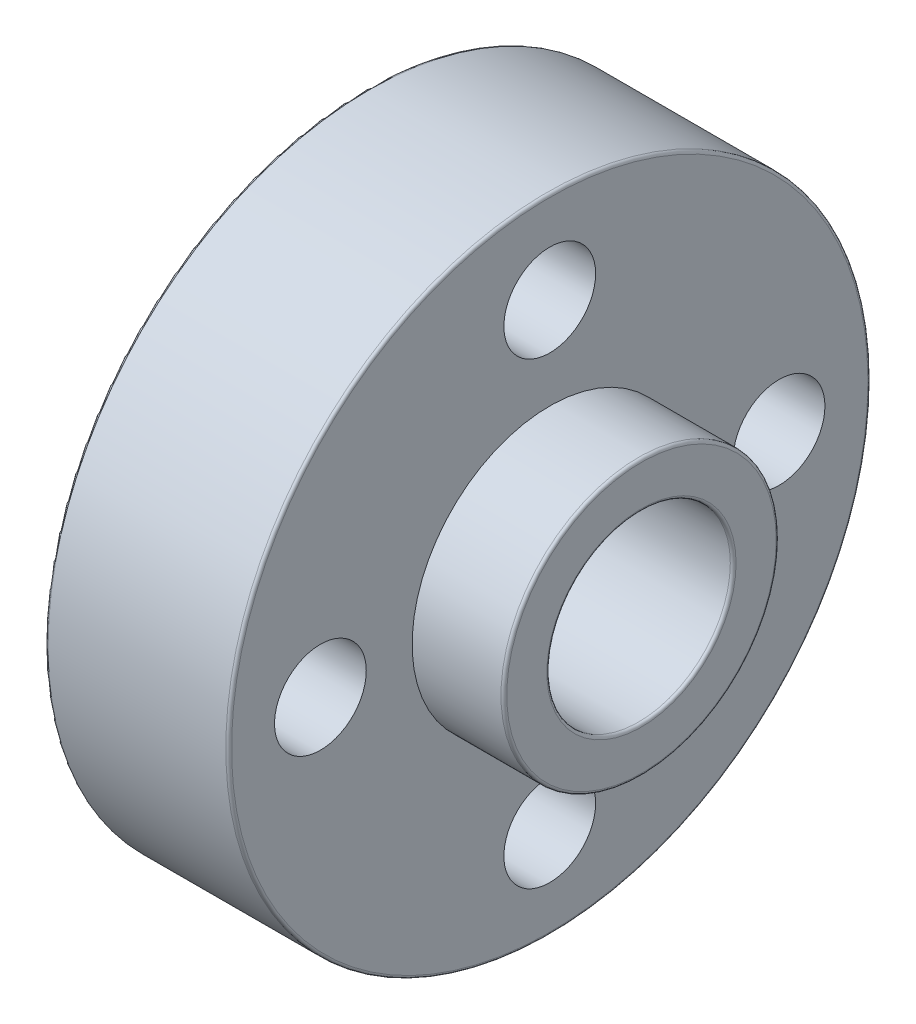
SolidWorks part; units mm, degrees
ref_plane "Front" through (0, 0, 0) normal (0, 0, 1) x (1, 0, 0)
ref_plane "Top" through (0, 0, 0) normal (0, 1, 0) x (1, 0, 0)
ref_plane "Right" through (0, 0, 0) normal (1, 0, 0) x (0, 0, -1)
sketch "Sketch1" plane through (0, 0, 0) normal (1, 0, 0) x (0, 0, -1)
  circle A0 centre (0, 0) radius 11.1125
  dimension "D1" = 22.225
extrude "Boss-Extrude1" add sketch "Sketch1" against normal blind 3.175
sketch "Sketch2" plane through (0, 0, 0) normal (1, 0, 0) x (0, 0, -1)
  circle A0 centre (0, 0) radius 4.7625
  dimension "D1" = 9.525
extrude "Boss-Extrude2" add sketch "Sketch2" along normal blind 3.175
sketch "Sketch4" plane through (3.175, 0, 0) normal (1, 0, 0) x (0, 0, -1)
  circle A0 centre (0, 0) radius 3.175
  dimension "D1" = 6.35
extrude "Cut-Extrude2" cut sketch "Sketch4" against normal through all
mirror "Mirror1" about plane through (-3.175, 0, 0) normal (1, 0, 0) of "Cut-Extrude2", "Boss-Extrude1", "Boss-Extrude2"
sketch "Sketch3" plane through (0, 0, 0) normal (1, 0, 0) x (0, 0, -1)
  line L0 (0, 0) -> (11.1125, 0) construction
  circle A0 centre (7.9375, 0) radius 1.5875
  circle A1 centre (0, 0) radius 11.1125 construction
  circle A2 centre (0, -7.9375) radius 1.5875
  circle A3 centre (-7.9375, 0) radius 1.5875
  circle A4 centre (0, 7.9375) radius 1.5875
  point P17 (0, 0)
  dimension "D1" = 3.175
  dimension "D2" = 7.9375
extrude "Cut-Extrude1" cut sketch "Sketch3" against normal through all
fillet "Fillet1" radius 0.1 6 edges at (3.175, 0, -3.175) (3.175, 0, -4.7625) (0, 0, -11.1125) (-9.525, 0, -3.175) (-9.525, 0, -4.7625) (-6.35, 0, -11.1125)
